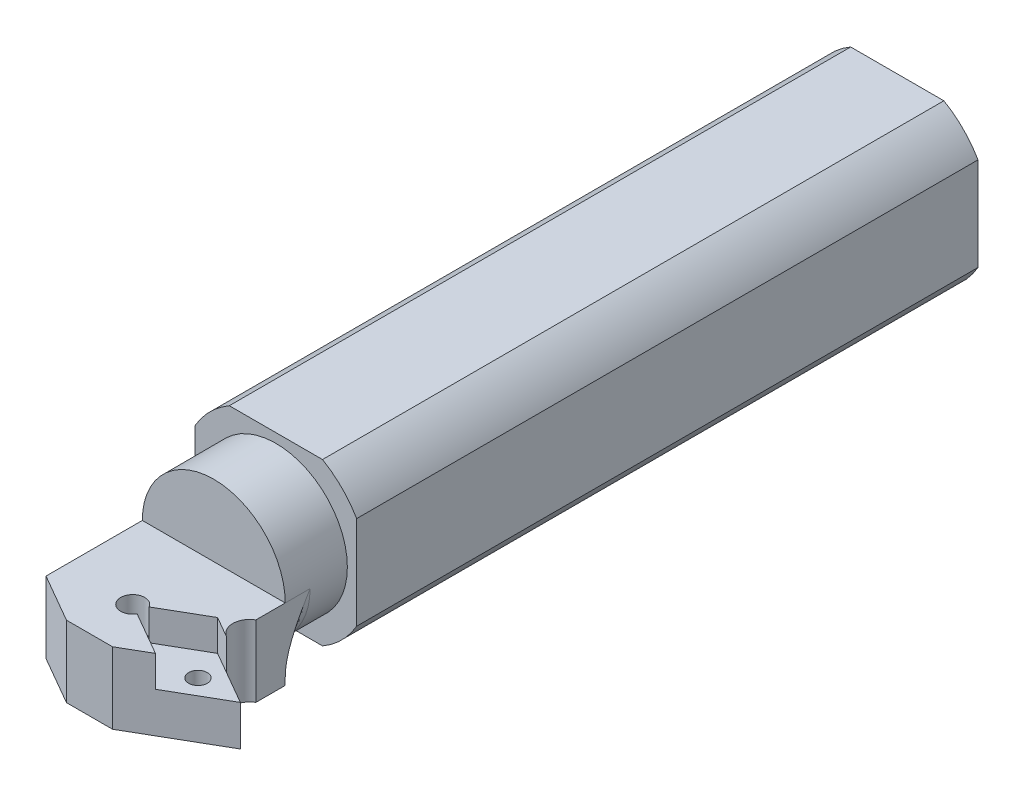
SolidWorks part; units mm, degrees
ref_plane "前视基准面" through (0, 0, 0) normal (0, 0, 1) x (1, 0, 0)
ref_plane "上视基准面" through (0, 0, 0) normal (0, 1, 0) x (1, 0, 0)
ref_plane "右视基准面" through (0, 0, 0) normal (1, 0, 0) x (0, 0, -1)
sketch "草图1" plane through (0, 0, 0) normal (0, 0, 1) x (1, 0, 0)
  line L0 (-7.5, 12.9904) -> (7.5, 12.9904)
  line L1 (12.9904, 7.5) -> (12.9904, -7.5)
  line L2 (7.5, -12.9904) -> (-7.5, -12.9904)
  line L3 (-12.9904, 7.5) -> (-12.9904, -7.5)
  arc A0 (-12.9904, -7.5) -> (-7.5, -12.9904) centre (0, 0) ccw
  arc A1 (12.9904, 7.5) -> (7.5, 12.9904) centre (0, 0) ccw
  arc A2 (7.5, -12.9904) -> (12.9904, -7.5) centre (0, 0) ccw
  arc A3 (-7.5, 12.9904) -> (-12.9904, 7.5) centre (0, 0) ccw
  dimension "D1" = 30
  dimension "D2" = 15
  dimension "D3" = 15
  dimension "D4" = 15
  dimension "D5" = 15
extrude "凸台-拉伸1" add sketch "草图1" along normal blind 100
sketch "草图2" plane through (0, 0, 100) normal (0, 0, 1) x (1, 0, 0)
  circle A0 centre (0, 0) radius 11.5
  dimension "D1" = 23
extrude "凸台-拉伸2" add sketch "草图2" along normal blind 10
sketch "草图3" plane through (0, 0, 110) normal (0, 0, 1) x (1, 0, 0)
  line L1 (-11.5, 0) -> (11.5, 0)
  line L2 (-11.5, 0) -> (-11.5, -11.5)
  line L3 (-11.5, -11.5) -> (11.5, -11.5)
  line L4 (11.5, 0) -> (11.5, -11.5)
  circle A0 centre (0, 0) radius 11.5 construction
extrude "凸台-拉伸3" add sketch "草图3" along normal blind 20
fillet "圆角3" radius 4 1 edges at (8.1317, -8.1317, 110) type face fillet first side face at (0, -1.5878, 110) second side face at (8.4606, -8.4606, 110)
fillet "圆角4" radius 4 2 edges at (-8.1317, -8.1317, 110) (0, -11.5, 108)
sketch "草图4" plane through (0, 0, 0) normal (0, 1, 0) x (1, 0, 0)
  line L0 (3.7058, -130) -> (11.5, -125.5)
  line L1 (11.5, -130) -> (-11.5, -130) construction
  line L2 (11.5, -130) -> (11.5, -110) construction
  line L3 (0, -110.94) -> (0, -144.4869) construction
  line L4 (11.5, -125.5) -> (11.5, -130)
  line L5 (11.5, -130) -> (3.7058, -130)
  line L6 (-11.5, -130) -> (-3.7058, -130)
  line L7 (-11.5, -125.5) -> (-11.5, -130)
  line L8 (-3.7058, -130) -> (-11.5, -125.5)
  dimension "D1" = 60
  dimension "D2" = 4.5
extrude "切除-拉伸1" cut sketch "草图4" against normal through all
sketch "草图5" plane through (0, 0, 0) normal (0, 1, 0) x (1, 0, 0)
  line L0 (11.5, -125.5) -> (16.7469, -122.4707)
  line L1 (16.7469, -122.4707) -> (11.5, -119.4415)
  line L2 (11.5, -125.5) -> (11.5, -110) construction
  line L3 (11.5, -119.4415) -> (11.5, -125.5)
  dimension "D1" = 60
extrude "凸台-拉伸4" add sketch "草图5" against normal up to surface (11.5 mm away) up to face at (0, -11.5, 117.7618)
sketch "草图6" plane through (0, 0, 0) normal (0, 1, 0) x (1, 0, 0)
  line L0 (11.5, -119.4415) -> (11.5, -110) construction
  line L1 (16.7469, -122.4707) -> (11.5, -119.4415) construction
  line L2 (11.5, -114.7207) -> (11.5, -119.4415)
  arc A0 (11.5, -119.4415) -> (11.5, -114.7207) centre (12.8628, -117.0811) cw
extrude "切除-拉伸2" cut sketch "草图6" against normal blind 20
sketch "草图7" plane through (0, 0, 0) normal (0, 1, 0) x (1, 0, 0)
  line L0 (16.7469, -122.4707) -> (8.0866, -127.4707)
  line L2 (8.0866, -127.4707) -> (1.1021, -123.4382)
  line L3 (16.7469, -122.4707) -> (8.0866, -117.4707)
  line L4 (8.0866, -127.4707) -> (8.0866, -109.3711) construction
  line L5 (1.1021, -121.5033) -> (8.0866, -117.4707)
  arc A0 (1.1021, -121.5033) -> (1.1021, -123.4382) centre (-0.5737, -122.4707) ccw
  dimension "D1" = 60
  dimension "D2" = 60
  dimension "D3" = 60
  dimension "D4" = 10
extrude "切除-拉伸3" cut sketch "草图7" against normal blind 5
sketch "草图8" plane through (0, -5, 0) normal (0, 1, 0) x (1, 0, 0)
  line L0 (-0.5737, -122.4707) -> (16.7469, -122.4707) construction
  circle A0 centre (9.9263, -122.4707) radius 1.5
  dimension "D2" = 3
  dimension "D1" = 10.5
extrude "切除-拉伸4" cut sketch "草图8" against normal through all
cosmetic thread "装饰螺纹线1" parameters "D2"=9
